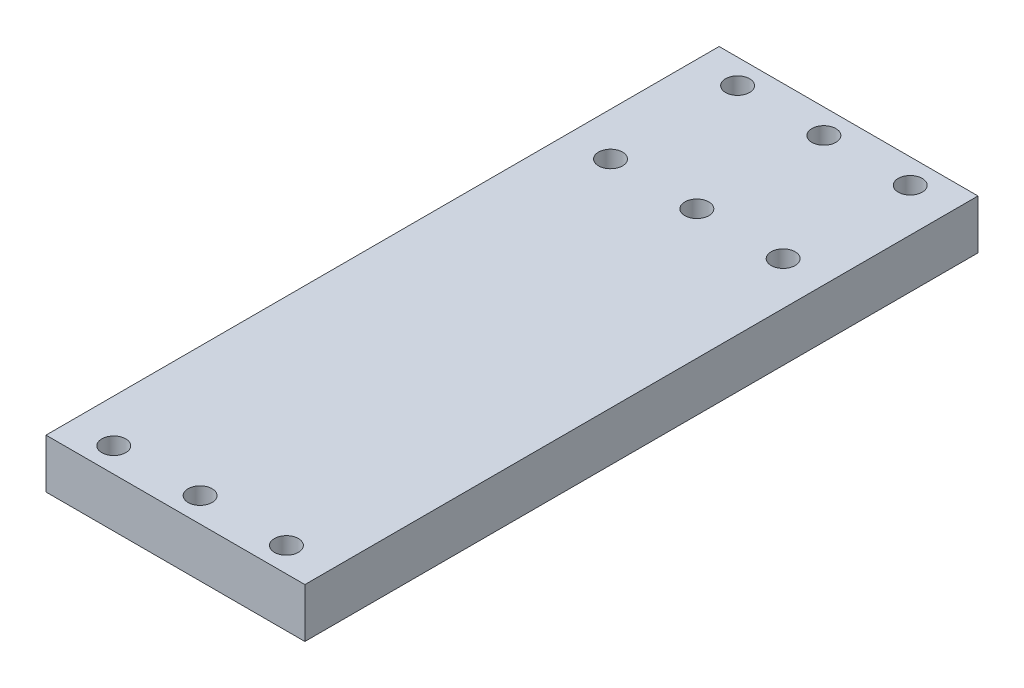
SolidWorks part; units mm, degrees
ref_plane "Front Plane" through (0, 0, 0) normal (0, 0, 1) x (1, 0, 0)
ref_plane "Top Plane" through (0, 0, 0) normal (0, 1, 0) x (1, 0, 0)
ref_plane "Right Plane" through (0, 0, 0) normal (1, 0, 0) x (0, 0, -1)
sketch "Sketch2" plane through (0, 0, 0) normal (0, 1, 0) x (1, 0, 0)
  line L1 (-25, -65) -> (25, -65)
  line L2 (-25, -65) -> (-25, 65)
  line L3 (-25, 65) -> (25, 65)
  line L4 (25, -65) -> (25, 65)
  line L5 (-25, -65) -> (25, 65) construction
  line L6 (-25, 65) -> (25, -65) construction
  point P0 (0, 0)
  dimension "D1" = 130
  dimension "D2" = 50
extrude "Boss-Extrude1" add sketch "Sketch2" along normal blind 9.525
sketch "Sketch3" plane through (0, 9.525, 0) normal (0, 1, 0) x (1, 0, 0)
  circle A0 centre (-16.67, -60.2375) radius 1.65 construction
  circle A1 centre (0, -60.2375) radius 1.65 construction
  circle A2 centre (16.67, -60.2375) radius 1.65 construction
  circle A3 centre (-16.67, 35.7) radius 1.65 construction
  circle A4 centre (0, 35.7) radius 1.65 construction
  circle A5 centre (16.67, 35.7) radius 1.65 construction
  circle A6 centre (-16.67, 60.2375) radius 1.65 construction
  circle A7 centre (0, 60.2375) radius 1.65 construction
  circle A8 centre (16.67, 60.2375) radius 1.65 construction
  circle A9 centre (-16.67, -60.2375) radius 1.65 construction
  circle A10 centre (0, -60.2375) radius 1.65 construction
  circle A11 centre (16.67, -60.2375) radius 1.65 construction
  circle A12 centre (-16.67, 35.7) radius 1.65 construction
  circle A13 centre (0, 35.7) radius 1.65 construction
  circle A14 centre (16.67, 35.7) radius 1.65 construction
  circle A15 centre (-16.67, 60.2375) radius 1.65 construction
  circle A16 centre (0, 60.2375) radius 1.65 construction
  circle A17 centre (16.67, 60.2375) radius 1.65 construction
  point P28 (-16.67, -60.2375)
  point P29 (0, -60.2375)
  point P30 (16.67, -60.2375)
  point P31 (-16.67, 35.7)
  point P32 (0, 35.7)
  point P33 (16.67, 35.7)
  point P34 (-16.67, 60.2375)
  point P35 (0, 60.2375)
  point P36 (16.67, 60.2375)
hole_wizard "M4 Clearance Hole1" positions "Sketch3" profile "Sketch4" hole size "M4" standard "ANSI Metric"
sketch "Sketch4" plane through (16.67, 9.525, -60.2375) normal (1, 0, 0) x (0, 0, 1)
  line L0 (0, 0) -> (0, 11.3925)
  line L1 (0, 11.3925) -> (2.3175, 10)
  line L2 (2.3175, 10) -> (2.3175, 0)
  line L5 (2.3175, 0) -> (0, 0)
  line L10 (0, 11.3925) -> (-2.3175, 10) construction
  line L11 (0, -6.35) -> (0, 107.95) construction
  dimension "Hole Dia." = 4.635
  dimension "Hole Depth" = 10
  dimension "Drill Angle" = 118
